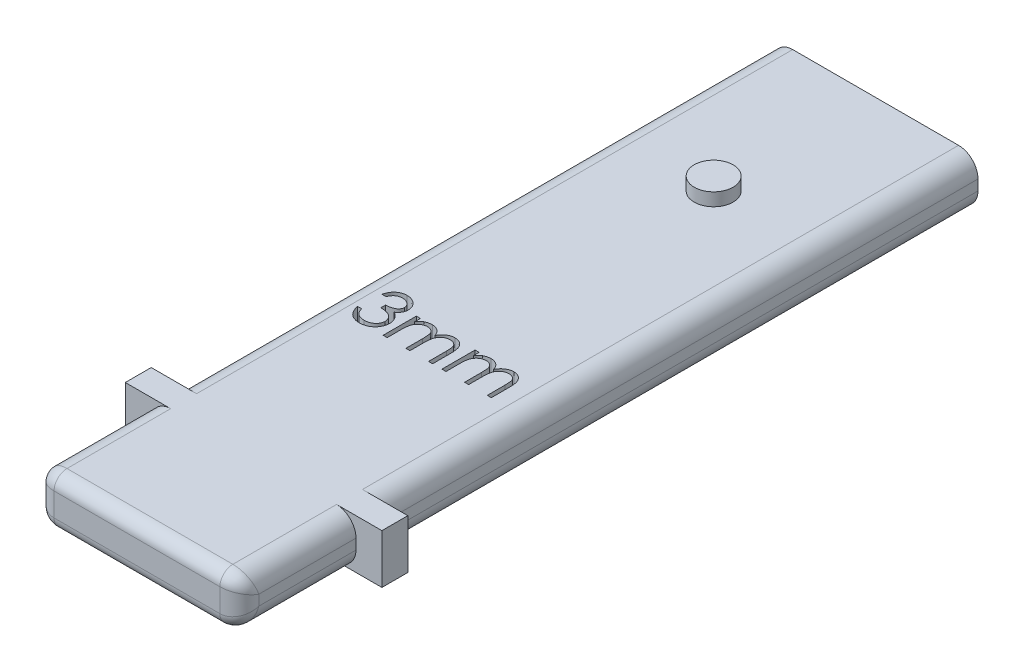
SolidWorks part; units mm, degrees
ref_plane "Front Plane" through (0, 0, 0) normal (0, 0, 1) x (1, 0, 0)
ref_plane "Top Plane" through (0, 0, 0) normal (0, 1, 0) x (1, 0, 0)
ref_plane "Right Plane" through (0, 0, 0) normal (1, 0, 0) x (0, 0, -1)
sketch "Sketch2" plane through (0, 0, 0) normal (0, 1, 0) x (1, 0, 0)
  line L1 (0, 0) -> (15.8, 0)
  line L2 (0, 0) -> (0, 57)
  line L3 (0, 57) -> (15.8, 57)
  line L4 (15.8, 0) -> (15.8, 57)
  dimension "D1" = 57
  dimension "D2" = 15.8
extrude "Boss-Extrude1" add sketch "Sketch2" along normal blind 3.8
fillet "Fillet3" radius 1 2 edges at (7.9, 0, 0) (7.9, 3.8, 0)
sketch "Sketch5" plane through (0, 3.8, 0) normal (0, 1, 0) x (1, 0, 0)
  line L0 (15.8, 57) -> (0, 57) construction
  circle A0 centre (7.9, 44.5) radius 1.5
  point P4 (7.9, 57)
  dimension "D1" = 3
  dimension "D2" = 12.5
extrude "Boss-Extrude4" add sketch "Sketch5" along normal blind 1
sketch "Sketch6" plane through (15.8, 0, 0) normal (1, 0, 0) x (0, 0, -1)
  line L0 (9, 3.8) -> (9, 0)
  line L1 (1, 3.8) -> (57, 3.8) construction
  line L2 (1, 0) -> (57, 0) construction
  line L3 (9, 0) -> (11, 0)
  line L4 (11, 0) -> (11, 3.8)
  line L5 (11, 3.8) -> (9, 3.8)
  line L6 (0, 2.8) -> (0, 1) construction
  dimension "D1" = 9
  dimension "D2" = 2
extrude "Boss-Extrude5" add sketch "Sketch6" along normal blind 2
sketch "Sketch7" plane through (0, 0, 0) normal (-1, 0, 0) x (0, 0, 1)
  line L0 (-57, 0) -> (-1, 0) construction
  line L1 (-9, 0) -> (-11, 0)
  line L2 (-9, 0) -> (-9, 3.8)
  line L3 (-9, 3.8) -> (-11, 3.8)
  line L4 (-11, 0) -> (-11, 3.8)
  line L5 (-57, 3.8) -> (-1, 3.8) construction
  line L6 (0, 2.8) -> (0, 1) construction
  dimension "D1" = 9
  dimension "D2" = 2
extrude "Boss-Extrude6" add sketch "Sketch7" along normal blind 2
fillet "Fillet4" radius 1.5 14 edges at (0, 0.2929, -0.2929) (0, 1.9, 0) (0, 3.5071, -0.2929) (15.8, 0.2929, -0.2929) (15.8, 1.9, 0) (15.8, 3.5071, -0.2929) (0, 0, -34) (0, 0, -5) (0, 3.8, -5) (0, 3.8, -34) (15.8, 0, -34) (15.8, 3.8, -34) (15.8, 0, -5) (15.8, 3.8, -5)
sketch "Sketch9" plane through (0, 3.8, 0) normal (0, 1, 0) x (1, 0, 0)
  text T0 "3mm"
extrude "Cut-Extrude1" cut sketch "Sketch9" against normal blind 5
